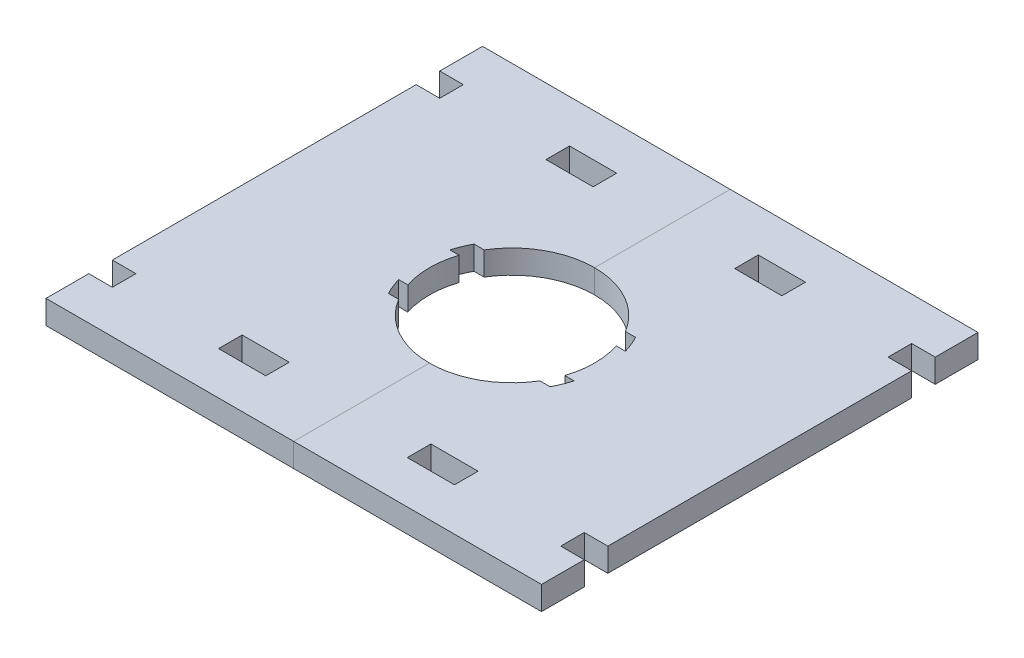
SolidWorks part; units mm, degrees
ref_plane "Front Plane" through (0, 0, 0) normal (0, 0, 1) x (1, 0, 0)
ref_plane "Top Plane" through (0, 0, 0) normal (0, 1, 0) x (1, 0, 0)
ref_plane "Right Plane" through (0, 0, 0) normal (1, 0, 0) x (0, 0, -1)
sketch "Sketch1" plane through (0, 0, 0) normal (0, 1, 0) x (1, 0, 0)
  line L0 (-15.5, 7.25) -> (-13.6999, 7.25) construction
  line L1 (-13.6999, -7.25) -> (-11.9765, -7.25)
  line L2 (-15.5, -7.25) -> (-15.5, -4.35) construction
  line L3 (-13.6999, 7.25) -> (-11.9765, 7.25)
  line L4 (15.5, 4.35) -> (15.5, 7.25) construction
  line L5 (-14.04, -6.5671) -> (-12.6813, -5.9316) construction
  line L6 (-14.04, 6.5671) -> (-12.6813, 5.9316) construction
  line L7 (-14.8771, -4.35) -> (-13.307, -4.35)
  line L8 (-15.5, -4.35) -> (-15.5, 0) construction
  line L9 (-14.8771, 4.35) -> (-13.307, 4.35)
  line L10 (15.5, 0) -> (15.5, 4.35) construction
  line L11 (-14.9234, -4.1882) -> (14.9234, 4.1882) construction
  line L12 (-14.9234, 4.1882) -> (14.9234, -4.1882) construction
  line L13 (-15.5, 7.25) -> (-14.04, 6.5671) construction
  line L14 (-15.5, 4.35) -> (-15.5, 7.25) construction
  line L15 (-15.5, 4.35) -> (-14.8771, 4.35) construction
  line L16 (-15.5, 4.35) -> (-14.9234, 4.1882) construction
  line L17 (-15.5, 0) -> (-15.5, 4.35) construction
  line L18 (-15.5, 0) -> (-15.5, 4.35) construction
  line L19 (-15.5, -4.35) -> (-15.5, 0) construction
  line L20 (-15.5, -4.35) -> (-14.9234, -4.1882) construction
  line L21 (-15.5, -4.35) -> (-14.8771, -4.35) construction
  line L22 (-15.5, -7.25) -> (-14.04, -6.5671) construction
  line L23 (-15.5, -7.25) -> (-13.6999, -7.25) construction
  line L24 (15.5, -7.25) -> (15.5, -4.35) construction
  line L25 (14.04, -6.5671) -> (15.5, -7.25) construction
  line L26 (13.6999, -7.25) -> (15.5, -7.25) construction
  line L27 (15.5, -4.35) -> (15.5, 0) construction
  line L28 (15.5, -4.35) -> (15.5, 0) construction
  line L29 (15.5, 0) -> (15.5, 4.35) construction
  line L30 (14.9234, 4.1882) -> (15.5, 4.35) construction
  line L31 (14.8771, 4.35) -> (15.5, 4.35) construction
  line L32 (13.6999, 7.25) -> (15.5, 7.25) construction
  line L33 (14.9234, -4.1882) -> (15.5, -4.35) construction
  line L34 (14.8771, -4.35) -> (15.5, -4.35) construction
  line L35 (-11.9765, 7.25) -> (11.9765, 7.25) construction
  line L36 (11.9765, 7.25) -> (13.6999, 7.25)
  line L37 (-9.3, 4.35) -> (9.3, 4.35) construction
  line L38 (13.307, 4.35) -> (14.8771, 4.35)
  line L39 (-12.6813, 5.9316) -> (-9.3, 4.35) construction
  line L40 (-9.3, 4.35) -> (9.3, -4.35) construction
  line L41 (-13.307, 4.35) -> (-9.3, 4.35) construction
  line L42 (-11.9765, -7.25) -> (11.9765, -7.25) construction
  line L43 (11.9765, -7.25) -> (13.6999, -7.25)
  line L44 (-9.3, -4.35) -> (9.3, -4.35) construction
  line L45 (13.307, -4.35) -> (14.8771, -4.35)
  line L46 (-12.6813, -5.9316) -> (-9.3, -4.35) construction
  line L47 (-9.3, -4.35) -> (9.3, 4.35) construction
  line L48 (-13.307, -4.35) -> (-9.3, -4.35) construction
  line L49 (9.3, -4.35) -> (13.307, -4.35) construction
  line L50 (9.3, -4.35) -> (12.6813, -5.9316) construction
  line L51 (12.6813, -5.9316) -> (14.04, -6.5671) construction
  line L52 (9.3, 4.35) -> (13.307, 4.35) construction
  line L53 (9.3, 4.35) -> (12.6813, 5.9316) construction
  line L54 (12.6813, 5.9316) -> (15.5, 7.25) construction
  arc A0 (-13.307, 4.35) -> (-13.307, -4.35) centre (0, 0) ccw
  arc A1 (-13.6999, 7.25) -> (-14.9234, 4.1882) centre (0, 0) ccw
  arc A2 (13.6999, 7.25) -> (-13.6999, 7.25) centre (0, 0) ccw construction
  arc A3 (-13.6999, -7.25) -> (13.6999, -7.25) centre (0, 0) ccw construction
  arc A4 (13.6999, -7.25) -> (14.9234, -4.1882) centre (0, 0) ccw
  arc A5 (15.5, 0) -> (14.9234, 4.1882) centre (0, 0) ccw construction
  arc A6 (14.9234, 4.1882) -> (13.6999, 7.25) centre (0, 0) ccw
  arc A7 (14.9234, -4.1882) -> (15.5, 0) centre (0, 0) ccw construction
  arc A8 (-14.9234, 4.1882) -> (-15.5, 0) centre (0, 0) ccw construction
  arc A9 (-14.9234, -4.1882) -> (-13.6999, -7.25) centre (0, 0) ccw
  arc A10 (-15.5, 0) -> (-14.9234, -4.1882) centre (0, 0) ccw construction
  arc A11 (-11.9765, 7.25) -> (-12.6813, 5.9316) centre (0, 0) ccw construction
  arc A12 (-12.6813, 5.9316) -> (-13.307, 4.35) centre (0, 0) ccw construction
  arc A13 (-12.6813, -5.9316) -> (-11.9765, -7.25) centre (0, 0) ccw construction
  arc A14 (-11.9765, -7.25) -> (11.9765, -7.25) centre (0, 0) ccw
  arc A15 (-13.307, -4.35) -> (-12.6813, -5.9316) centre (0, 0) ccw construction
  arc A16 (12.6813, -5.9316) -> (13.307, -4.35) centre (0, 0) ccw construction
  arc A17 (13.307, -4.35) -> (-11.9765, 7.25) centre (0, 0) ccw
  arc A18 (11.9765, -7.25) -> (12.6813, -5.9316) centre (0, 0) ccw construction
  dimension "D1" = 28
  dimension "D2" = 31
  dimension "D3" = 14.5
  dimension "D4" = 8.7
sketch "Sketch2" plane through (0, 0, 0) normal (0, 1, 0) x (1, 0, 0)
  line L0 (13.307, -4.35) -> (14.8771, -4.35) construction
  line L1 (-13.6999, 7.25) -> (-11.9765, 7.25) construction
  line L2 (-14.8771, -4.35) -> (-13.307, -4.35) construction
  line L3 (-14.8771, 4.35) -> (-13.307, 4.35) construction
  line L4 (11.9765, -7.25) -> (13.6999, -7.25) construction
  line L5 (-13.6999, -7.25) -> (-11.9765, -7.25) construction
  line L6 (11.9765, 7.25) -> (13.6999, 7.25) construction
  line L7 (13.307, 4.35) -> (14.8771, 4.35) construction
  line L8 (13.307, -4.35) -> (14.8771, -4.35)
  line L9 (-13.6999, 7.25) -> (-11.9765, 7.25)
  line L10 (-14.8771, -4.35) -> (-13.307, -4.35)
  line L11 (-14.8771, 4.35) -> (-13.307, 4.35)
  line L12 (11.9765, -7.25) -> (13.6999, -7.25)
  line L13 (-13.6999, -7.25) -> (-11.9765, -7.25)
  line L14 (11.9765, 7.25) -> (13.6999, 7.25)
  line L15 (13.307, 4.35) -> (14.8771, 4.35)
  line L17 (-42, -37) -> (42, -37)
  line L18 (-42, -37) -> (-42, 37)
  line L19 (-42, 37) -> (42, 37)
  line L20 (42, -37) -> (42, 37)
  line L21 (-42, -37) -> (42, 37) construction
  line L22 (-42, 37) -> (42, -37) construction
  arc A0 (13.307, -4.35) -> (-11.9765, 7.25) centre (0, 0) ccw construction
  arc A1 (-13.6999, 7.25) -> (-14.9234, 4.1882) centre (0, 0) ccw construction
  arc A2 (-13.307, 4.35) -> (-13.307, -4.35) centre (0, 0) ccw construction
  arc A3 (13.6999, -7.25) -> (14.9234, -4.1882) centre (0, 0) ccw construction
  arc A4 (-11.9765, -7.25) -> (11.9765, -7.25) centre (0, 0) ccw construction
  arc A5 (-14.9234, -4.1882) -> (-13.6999, -7.25) centre (0, 0) ccw construction
  arc A6 (14.9234, 4.1882) -> (13.6999, 7.25) centre (0, 0) ccw construction
  arc A7 (13.307, -4.35) -> (-11.9765, 7.25) centre (0, 0) ccw
  arc A8 (-13.6999, 7.25) -> (-14.9234, 4.1882) centre (0, 0) ccw
  arc A9 (-13.307, 4.35) -> (-13.307, -4.35) centre (0, 0) ccw
  arc A10 (13.6999, -7.25) -> (14.9234, -4.1882) centre (0, 0) ccw
  arc A11 (-11.9765, -7.25) -> (11.9765, -7.25) centre (0, 0) ccw
  arc A12 (-14.9234, -4.1882) -> (-13.6999, -7.25) centre (0, 0) ccw
  arc A13 (14.9234, 4.1882) -> (13.6999, 7.25) centre (0, 0) ccw
  dimension "D1" = 84
  dimension "D2" = 74
extrude "Boss-Extrude1" add sketch "Sketch2" along normal blind 4 contours L17 L20 L19 L18 A13 L15 A7 L8 A10 L12 A11 L13 A12 L10 A9 L11 A8 L9 L14 region at (-40.8805, 0, 0)
split "Split1" trim tools "Right Plane" bodies to split 101 resulting bodies 102 103
sketch "Sketch4" plane through (0, 4, 0) normal (0, 1, 0) x (1, 0, 0)
  line L0 (0, -18.5) -> (42, -18.5) construction
  line L2 (42, -37) -> (42, 37) construction
  line L3 (0, -18.5) -> (0, -37) construction
  line L4 (-42, -37) -> (-42, 37) construction
  line L5 (-20, -29.75) -> (-12, -29.75)
  line L6 (-20, -29.75) -> (-20, -25.75)
  line L7 (-20, -25.75) -> (-12, -25.75)
  line L8 (-12, -29.75) -> (-12, -25.75)
  line L9 (-20, -29.75) -> (-12, -25.75) construction
  line L10 (-20, -25.75) -> (-12, -29.75) construction
  line L11 (-42, -29.75) -> (-38, -29.75)
  line L12 (-42, -29.75) -> (-42, -25.75)
  line L13 (-42, -25.75) -> (-38, -25.75)
  line L14 (-38, -29.75) -> (-38, -25.75)
  line L15 (-42, -29.75) -> (-38, -25.75) construction
  line L16 (-42, -25.75) -> (-38, -29.75) construction
  line L17 (0, 0) -> (0, -37) construction
  line L18 (-14.9234, 4.1882) -> (14.9234, -4.1882) construction
  line L33 (42, -25.75) -> (38, -29.75) construction
  line L34 (42, -29.75) -> (38, -25.75) construction
  line L35 (20, -25.75) -> (12, -29.75) construction
  line L36 (20, -29.75) -> (12, -25.75) construction
  line L45 (38, -29.75) -> (38, -25.75)
  line L46 (42, -25.75) -> (38, -25.75)
  line L47 (42, -29.75) -> (42, -25.75)
  line L48 (42, -29.75) -> (38, -29.75)
  line L49 (12, -29.75) -> (12, -25.75)
  line L50 (20, -25.75) -> (12, -25.75)
  line L51 (20, -29.75) -> (20, -25.75)
  line L52 (20, -29.75) -> (12, -29.75)
  line L53 (-2.2, 0) -> (2.2, 0) construction
  line L54 (20, 29.75) -> (12, 25.75) construction
  line L55 (20, 25.75) -> (12, 29.75) construction
  line L56 (42, 29.75) -> (38, 25.75) construction
  line L57 (42, 25.75) -> (38, 29.75) construction
  line L58 (20, 29.75) -> (12, 29.75)
  line L59 (20, 29.75) -> (20, 25.75)
  line L60 (20, 25.75) -> (12, 25.75)
  line L61 (12, 29.75) -> (12, 25.75)
  line L62 (42, 29.75) -> (38, 29.75)
  line L63 (42, 29.75) -> (42, 25.75)
  line L64 (42, 25.75) -> (38, 25.75)
  line L65 (38, 29.75) -> (38, 25.75)
  line L82 (-42, 25.75) -> (-38, 29.75) construction
  line L83 (-42, 29.75) -> (-38, 25.75) construction
  line L84 (-20, 25.75) -> (-12, 29.75) construction
  line L85 (-20, 29.75) -> (-12, 25.75) construction
  line L94 (-38, 29.75) -> (-38, 25.75)
  line L95 (-42, 25.75) -> (-38, 25.75)
  line L96 (-42, 29.75) -> (-42, 25.75)
  line L97 (-42, 29.75) -> (-38, 29.75)
  line L98 (-12, 29.75) -> (-12, 25.75)
  line L99 (-20, 25.75) -> (-12, 25.75)
  line L100 (-20, 29.75) -> (-20, 25.75)
  line L101 (-20, 29.75) -> (-12, 29.75)
  point P6 (-16, -27.75)
  point P14 (0, -27.75)
  point P15 (-40, -27.75)
  point P53 (40, -27.75)
  point P54 (16, -27.75)
  point P65 (16, 27.75)
  point P66 (40, 27.75)
  point P95 (-40, 27.75)
  point P96 (-16, 27.75)
  dimension "D1" = 4
  dimension "D2" = 8
  dimension "D3" = 20
  dimension "D4" = 4
extrude "Cut-Extrude2" cut sketch "Sketch4" against normal through all both
equation "\"m3_hole\"= 3.5"
equation "\"m3_washer\"= 7.3"
equation "\"m3_nut\"= 5.3"
equation "\"guide_width\"= 10.0"
equation "\"guide_length\"= 65.0"
equation "\"guide_tab_length\" = 10.0"
equation "\"guide_tab_width\" = 9.0"
equation "\"guide_thickness\" = 12.0"
equation "\"grinder_od\"= 52.0"
equation "\"grinder_id\"= 45.5"
equation "\"grinder_adjust_od\" = 58.0"
equation "\"funnel_width_from_adjust_ring\" = 13.0"
equation "\"drill_contact_diameter_small\" = 24.0"
equation "\"drill_contact_diameter_medium\" = 28.0"
equation "\"drill_contact_diameter_large\" = 39.0"
equation "\"drill_contact_diameter_tab\" = 31.0"
equation "\"drill_contact_ow_tab\" = 14.5"
equation "\"drill_contact_iw_tab\" = 8.7"
equation "\"drill_contact_small_height\" = 15.5"
equation "\"drill_contact_large_height\" = 34.5"
equation "\"D1@Sketch1\"=\"drill_contact_diameter_medium\""
equation "\"D2@Sketch1\"=\"drill_contact_diameter_tab\""
equation "\"D3@Sketch1\"=\"drill_contact_ow_tab\""
equation "\"D1@Sketch2\"=\"grinder_od\"+\"guide_thickness\"+20"
equation "\"D2@Sketch2\"=\"grinder_od\"+\"guide_thickness\"+\"guide_tab_length\""
equation "\"plywood_thickness\" = 4.0"
equation "\"D4@Sketch1\"=\"drill_contact_iw_tab\""
equation "\"plywood_peg_length\" = 40.0"
equation "\"plywood_peg_width\" = 8.0"
equation "\"D3@Sketch4\"=\"plywood_peg_length\"/2"
equation "\"D2@Sketch4\"=\"plywood_peg_width\""
